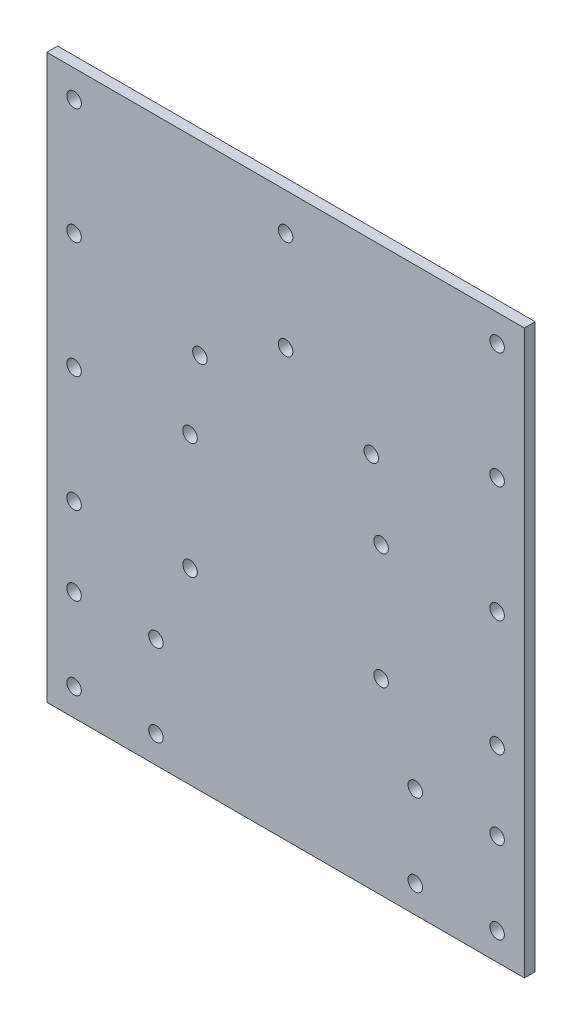
SolidWorks part; units mm, degrees
ref_plane "Front Plane" through (0, 0, 0) normal (0, 0, 1) x (1, 0, 0)
ref_plane "Top Plane" through (0, 0, 0) normal (0, 1, 0) x (1, 0, 0)
ref_plane "Right Plane" through (0, 0, 0) normal (1, 0, 0) x (0, 0, -1)
sketch "Sketch1" plane through (0, 0, 0) normal (0, 0, 1) x (1, 0, 0)
  line L0 (0, 82.5) -> (0, -82.5) construction
  line L1 (-70, -82.5) -> (70, -82.5)
  line L2 (-70, -82.5) -> (-70, 82.5)
  line L3 (-70, 82.5) -> (70, 82.5)
  line L4 (70, -82.5) -> (70, 82.5)
  line L5 (-70, -82.5) -> (70, 82.5) construction
  line L6 (-70, 82.5) -> (70, -82.5) construction
  line L7 (-50, -78.3304) -> (-50, -60.5714) construction
  line L10 (-62, -62.5) -> (-36.3402, -62.5) construction
  circle A0 centre (0, 42.5) radius 33.35 construction
  circle A1 centre (0, 42.5) radius 29 construction
  circle A2 centre (0, 71.5) radius 2.125
  circle A3 centre (25.1147, 28) radius 2.125
  circle A4 centre (-25.1147, 28) radius 2.125
  circle A10 centre (0, 42.5) radius 2.125
  circle A11 centre (-62, -74.5) radius 2.125
  circle A12 centre (-38, -74.5) radius 2.125
  circle A13 centre (-38, -50.5) radius 2.125
  circle A14 centre (-62, -50.5) radius 2.125
  circle A15 centre (38, -74.5) radius 2.125
  circle A16 centre (62, -74.5) radius 2.125
  circle A17 centre (62, -50.5) radius 2.125
  circle A18 centre (38, -50.5) radius 2.125
  point P0 (0, 0)
  point P19 (0, 42.5)
  dimension "D3" = 66.7
  dimension "D4" = 40
  dimension "D5" = 58
  dimension "D6" = 4.25
  dimension "D8" = 4.25
  dimension "D9" = 8
  dimension "D10" = 8
  dimension "D12" = 4.25
  dimension "D1" = 140
  dimension "D2" = 165
  dimension "D11" = 12
  dimension "D13" = 12
  dimension "D7" = 3
extrude "Boss-Extrude1" add sketch "Sketch1" along normal blind 3.175
sketch "Sketch2" plane through (0, 0, 3.175) normal (0, 0, 1) x (1, 0, 0)
  line L0 (70, 82.5) -> (-70, 82.5) construction
  line L1 (-70, 82.5) -> (-70, -82.5) construction
  line L2 (0, 82.5) -> (0, -82.5) construction
  line L3 (-70, -82.5) -> (70, -82.5) construction
  circle A0 centre (-62, 74.5) radius 2.125
  circle A1 centre (-62, 40.5) radius 2.125
  circle A2 centre (-62, 6.5) radius 2.125
  circle A3 centre (-62, -27.5) radius 2.125
  circle A4 centre (-28, 6.5) radius 2.125
  circle A5 centre (-28, -27.5) radius 2.125
  circle A6 centre (28, -27.5) radius 2.125
  circle A7 centre (28, 6.5) radius 2.125
  circle A8 centre (62, -27.5) radius 2.125
  circle A9 centre (62, 6.5) radius 2.125
  circle A10 centre (62, 40.5) radius 2.125
  circle A11 centre (62, 74.5) radius 2.125
  dimension "D1" = 4.25
  dimension "D2" = 8
  dimension "D3" = 8
  dimension "D4" = 4
  dimension "D5" = 2
extrude "Cut-Extrude1" cut sketch "Sketch2" against normal through all
